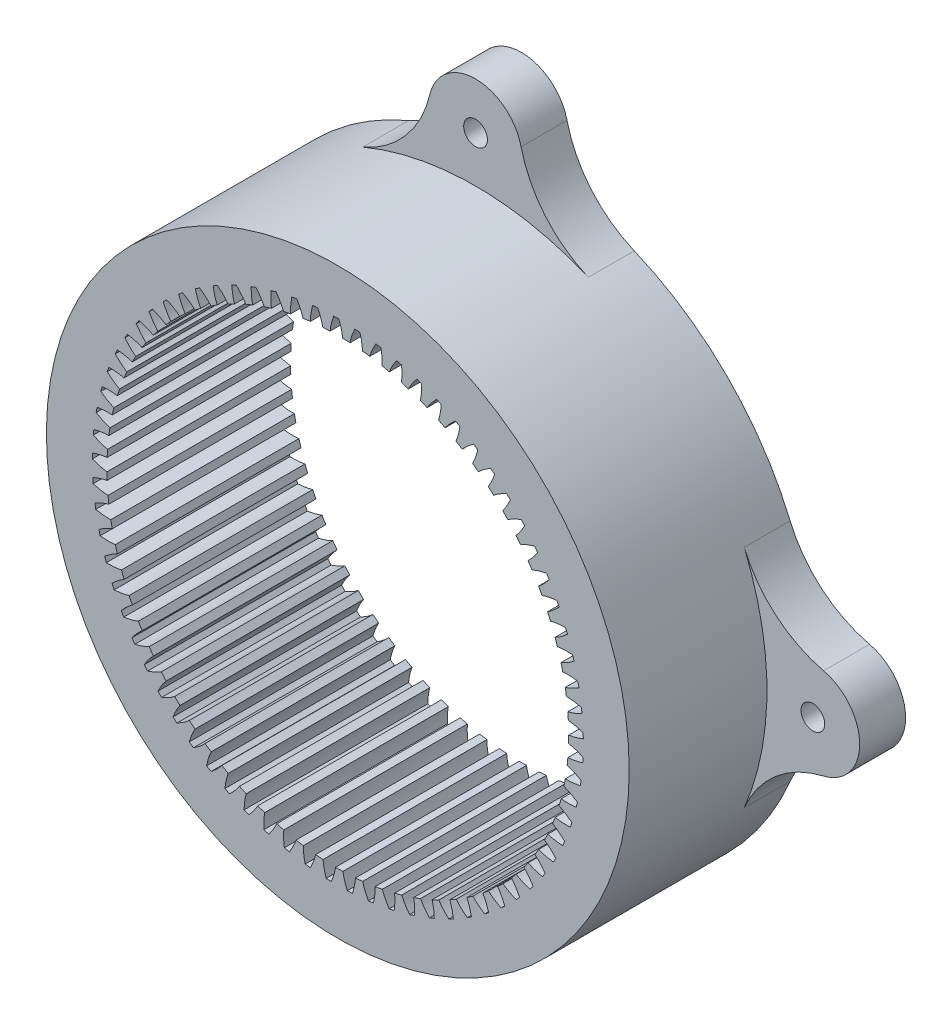
SolidWorks part; units mm, degrees
ref_plane "Front Plane" through (0, 0, 0) normal (0, 0, 1) x (1, 0, 0)
ref_plane "Top Plane" through (0, 0, 0) normal (0, 1, 0) x (1, 0, 0)
ref_plane "Right Plane" through (0, 0, 0) normal (1, 0, 0) x (0, 0, -1)
sketch "Sketch1" plane through (0, 0, 0) normal (0, 0, 1) x (1, 0, 0)
  circle A1 centre (0, 0) radius 38.0875
  dimension "D1" = 76.175
extrude "Boss-Extrude1" add sketch "Sketch1" along normal blind 24
sketch "Sketch2" plane through (0, 0, 24) normal (0, 0, 1) x (1, 0, 0)
  line L0 (0, 0) -> (38.0845, 0.4788) construction
  line L1 (0, 0) -> (38.0567, 1.5322) construction
  line L2 (0, 0) -> (37.9997, 2.5844) construction
  line L3 (4.4804, -8.2514) -> (4.4804, -8.1337) construction
  circle A0 centre (0, 0) radius 32.0875
  circle A1 centre (0, 0) radius 31.025 construction
  circle A2 centre (0, 0) radius 30.175
  circle A3 centre (0, 0) radius 29.9678 construction
  circle A4 centre (0, 0) radius 38.0875 construction
  spline S0 degree 4 poles (29.9678, 0) (29.99, 0.0005) (30.0521, 0.0032) (30.1692, 0.0142) (30.3596, 0.0402) (30.6006, 0.0851) (30.9099, 0.1568) (31.2707, 0.2585) (31.663, 0.3882) (32.0843, 0.5484) (32.4994, 0.7251) (32.9079, 0.9166) (33.3099, 1.1214) (33.7897, 1.3848) (34.3562, 1.724) (35.0016, 2.1498) (35.7167, 2.6727) (36.42, 3.2384) (37.098, 3.8335) (37.7517, 4.456) (38.3804, 5.1026) (38.91, 5.6892) (39.3478, 6.2034) (39.7045, 6.6428) (39.9809, 6.9942) (40.2576, 7.36) (40.5173, 7.7126) (40.7904, 8.0994) (41.0245, 8.4384) (41.3601, 8.9465) (41.5555, 9.2539) (41.8638, 9.751) (41.9939, 9.9761) (42.1149, 10.1791) (42.1485, 10.2393) (42.174, 10.2833) (42.1879, 10.307) knots 0 0 0 0 0 0.005377 0.015084 0.028532 0.04661 0.064855 0.092111 0.119476 0.146842 0.174209 0.201575 0.228941 0.256307 0.307035 0.361767 0.4165 0.471232 0.525964 0.580697 0.635429 0.690161 0.717528 0.744894 0.77226 0.799626 0.826992 0.854358 0.881725 0.909091 0.954545 0.977273 0.988636 0.994318 1 1 1 1 1 construction
  spline S1 degree 4 poles (29.9678, 0) (29.99, 0.0005) (30.0521, 0.0032) (30.1692, 0.0142) (30.3596, 0.0402) (30.6006, 0.0851) (30.9099, 0.1568) (31.2707, 0.2585) (31.663, 0.3882) (32.0843, 0.5484) (32.4994, 0.7251) (32.9079, 0.9166) (33.3099, 1.1214) (33.7897, 1.3848) (34.3562, 1.724) (35.0016, 2.1498) (35.7167, 2.6727) (36.42, 3.2384) (37.098, 3.8335) (37.7517, 4.456) (38.3804, 5.1026) (38.91, 5.6892) (39.3478, 6.2034) (39.7045, 6.6428) (39.9809, 6.9942) (40.2576, 7.36) (40.5173, 7.7126) (40.7904, 8.0994) (41.0245, 8.4384) (41.2405, 8.7654) (41.3534, 8.9391) (41.4088, 9.0254) knots 0 0 0 0 0 0.005377 0.015084 0.028532 0.04661 0.064855 0.092111 0.119476 0.146842 0.174209 0.201575 0.228941 0.256307 0.307035 0.361767 0.4165 0.471232 0.525964 0.580697 0.635429 0.690161 0.717528 0.744894 0.77226 0.799626 0.826992 0.854358 0.881725 0.909091 0.909091 0.909091 0.909091 0.909091
  spline S2 degree 4 poles (29.922, 1.6574) (29.9441, 1.6582) (30.0063, 1.6589) (30.1238, 1.6544) (30.3153, 1.639) (30.5585, 1.6074) (30.8712, 1.553) (31.2372, 1.4714) (31.636, 1.3635) (32.0655, 1.2269) (32.4898, 1.0734) (32.9082, 0.9049) (33.3209, 0.7226) (33.8146, 0.4861) (34.399, 0.1788) (35.0669, -0.2107) (35.8099, -0.6932) (36.5433, -1.2191) (37.2533, -1.7758) (37.9403, -2.3613) (38.6038, -2.9721) (39.165, -3.5285) (39.6307, -4.0177) (40.0111, -4.4367) (40.3065, -4.7723) (40.6031, -5.1222) (40.8818, -5.4599) (41.176, -5.831) (41.4284, -6.1566) (41.7916, -6.6453) (42.0037, -6.9414) (42.3391, -7.4207) (42.4813, -7.6383) (42.6134, -7.8343) (42.6503, -7.8926) (42.6782, -7.9351) (42.6934, -7.958) knots 0 0 0 0 0 0.005377 0.015084 0.028532 0.04661 0.064855 0.092111 0.119476 0.146842 0.174209 0.201575 0.228941 0.256307 0.307035 0.361767 0.4165 0.471232 0.525964 0.580697 0.635429 0.690161 0.717528 0.744894 0.77226 0.799626 0.826992 0.854358 0.881725 0.909091 0.954545 0.977273 0.988636 0.994318 1 1 1 1 1 construction
  spline S3 degree 4 poles (29.922, 1.6574) (29.9441, 1.6582) (30.0063, 1.6589) (30.1238, 1.6544) (30.3153, 1.639) (30.5585, 1.6074) (30.8712, 1.553) (31.2372, 1.4714) (31.636, 1.3635) (32.0655, 1.2269) (32.4898, 1.0734) (32.9082, 0.9049) (33.3209, 0.7226) (33.8146, 0.4861) (34.399, 0.1788) (35.0669, -0.2107) (35.8099, -0.6932) (36.5433, -1.2191) (37.2533, -1.7758) (37.9403, -2.3613) (38.6038, -2.9721) (39.165, -3.5285) (39.6307, -4.0177) (40.0111, -4.4367) (40.3065, -4.7723) (40.6031, -5.1222) (40.8818, -5.4599) (41.176, -5.831) (41.4284, -6.1566) (41.6622, -6.4711) (41.7845, -6.6383) (41.8446, -6.7214) knots 0 0 0 0 0 0.005377 0.015084 0.028532 0.04661 0.064855 0.092111 0.119476 0.146842 0.174209 0.201575 0.228941 0.256307 0.307035 0.361767 0.4165 0.471232 0.525964 0.580697 0.635429 0.690161 0.717528 0.744894 0.77226 0.799626 0.826992 0.854358 0.881725 0.909091 0.909091 0.909091 0.909091 0.909091
  point P6 (0, 0)
  dimension "D5" = 1.585
  dimension "D6" = 1.585
sketch "Sketch5" plane through (0, 0, 24) normal (0, 0, 1) x (1, 0, 0)
  circle A0 centre (0, 0) radius 30.175 construction
  circle A1 centre (0, 0) radius 30.175
extrude "Cut-Extrude1" cut sketch "Sketch5" against normal through all
sketch "Sketch6" plane through (0, 0, 24) normal (0, 0, 1) x (1, 0, 0)
  circle A0 centre (0, 0) radius 32.0875 construction
  arc A1 (32.0828, 0.5518) -> (32.0642, 1.2235) centre (0, 0) ccw
  spline S0 degree 4 poles (133.1254, -1995.4815) (26.6738, -33.7924) (26.6919, 0.8301) (28.5037, 1.7849) (30.3153, 1.639) (30.5585, 1.6074) (30.8712, 1.553) (31.2372, 1.4714) (31.636, 1.3635) (32.0655, 1.2269) (32.4898, 1.0734) (32.9082, 0.9049) (33.3209, 0.7226) (33.8146, 0.4861) (34.399, 0.1788) (35.0669, -0.2107) (35.8099, -0.6932) (36.5433, -1.2191) (37.2533, -1.7758) (37.9403, -2.3613) (38.6038, -2.9721) (39.165, -3.5285) (39.6307, -4.0177) (40.0111, -4.4367) (40.3065, -4.7723) (40.6031, -5.1222) (40.8818, -5.4599) (41.176, -5.831) (42.4699, -7.4998) (45.582, -12.0642) (7.971, 39.4031) (1213.0845, -1627.696) knots -0.394366 -0.394366 -0.394366 -0.394366 -0.394366 0.005377 0.015084 0.028532 0.04661 0.064855 0.092111 0.119476 0.146842 0.174209 0.201575 0.228941 0.256307 0.307035 0.361767 0.4165 0.471232 0.525964 0.580697 0.635429 0.690161 0.717528 0.744894 0.77226 0.799626 0.826992 0.854358 0.881725 1.360788 1.360788 1.360788 1.360788 1.360788 only from (29.922, 1.6574) to (41.8446, -6.7214) construction
  spline S1 degree 4 poles (22.5577, 1999.79) (24.764, 35.2159) (26.697, 0.6474) (28.5588, -0.2057) (30.3596, 0.0402) (30.6006, 0.0851) (30.9099, 0.1568) (31.2707, 0.2585) (31.663, 0.3882) (32.0843, 0.5484) (32.4994, 0.7251) (32.9079, 0.9166) (33.3099, 1.1214) (33.7897, 1.3848) (34.3562, 1.724) (35.0016, 2.1498) (35.7167, 2.6727) (36.42, 3.2384) (37.098, 3.8335) (37.7517, 4.456) (38.3804, 5.1026) (38.91, 5.6892) (39.3478, 6.2034) (39.7045, 6.6428) (39.9809, 6.9942) (40.2576, 7.36) (40.5173, 7.7126) (40.7904, 8.0994) (41.9901, 9.8372) (44.845, 14.5668) (10.1381, -38.902) (1121.205, 1692.2966) knots -0.394366 -0.394366 -0.394366 -0.394366 -0.394366 0.005377 0.015084 0.028532 0.04661 0.064855 0.092111 0.119476 0.146842 0.174209 0.201575 0.228941 0.256307 0.307035 0.361767 0.4165 0.471232 0.525964 0.580697 0.635429 0.690161 0.717528 0.744894 0.77226 0.799626 0.826992 0.854358 0.881725 1.360788 1.360788 1.360788 1.360788 1.360788 only from (29.9678, 0) to (41.4088, 9.0254) construction
  spline S2 degree 4 poles (29.922, 1.6574) (29.9441, 1.6582) (30.0063, 1.6589) (30.1238, 1.6544) (30.3153, 1.639) (30.5585, 1.6074) (30.8712, 1.553) (31.2372, 1.4714) (31.5815, 1.3783) (31.8503, 1.2949) (32.0108, 1.2416) (32.0642, 1.2235) knots 0 0 0 0 0 0.005377 0.015084 0.028532 0.04661 0.064855 0.092111 0.119476 0.13315 0.13315 0.13315 0.13315 0.13315
  spline S3 degree 4 poles (29.9678, 0) (29.99, 0.0005) (30.0521, 0.0032) (30.1692, 0.0142) (30.3596, 0.0402) (30.6006, 0.0851) (30.9099, 0.1568) (31.2707, 0.2585) (31.6094, 0.3705) (31.8732, 0.4686) (32.0305, 0.5307) (32.0828, 0.5518) knots 0 0 0 0 0 0.005377 0.015084 0.028532 0.04661 0.064855 0.092111 0.119476 0.13315 0.13315 0.13315 0.13315 0.13315
extrude "Cut-Extrude2" cut sketch "Sketch6" against normal through all and the other way through all
pattern_circular "CirPattern2" count 73 over 360 about axis through (0, 0, 24) along (0, 0, -1) of "Cut-Extrude2"
sketch "Sketch7" plane through (0, 0, 0) normal (0, 0, 1) x (1, 0, 0)
  line L0 (0, 0) -> (-44.0875, 0) construction
  line L1 (-44.0875, 6.1201) -> (-37.5926, 6.1201)
  line L2 (-44.0875, -6.1201) -> (-37.5926, -6.1201)
  circle A2 centre (-44.0875, 0) radius 1.55
  arc A3 (-44.0875, 6.1201) -> (-44.0875, -6.1201) centre (-44.0875, 0) ccw
  circle A5 centre (0, 0) radius 38.0875 construction
  arc A6 (-37.5926, 6.1201) -> (-37.5926, -6.1201) centre (0, 0) ccw
  dimension "D2" = 3.1
  dimension "D3" = 12.2403
  dimension "D1" = 44.0875
extrude "Boss-Extrude3" add sketch "Sketch7" along normal blind 6
fillet "Fillet1" radius 15 2 edges at (-37.5926, 6.1201, 3) (-37.5926, -6.1201, 3)
pattern_circular "CirPattern5" count 4 over 360 about axis through (0, 0, 0) along (0, 0, 1) of "Fillet1", "Boss-Extrude3"
ref_plane "Plane1" through (0, 0, 16) normal (0, 0, 1) x (1, 0, 0)
equation "\"P`\"= \"N\" / \"dp\"'Diametral pitch - number of teeth per mm"
equation "\"N\"= 73'# of teeth"
equation "\"phi\"= 15deg'Pressure angle"
equation "\"a\"= 1 / \"P`\"'Addendum"
equation "\"b\"= 1.25 / \"P`\"'Dedendum"
equation "\"c\"= \"b\" - \"a\"'clearance"
equation "\"dp\"= \"dp_from_mod\"'pitch cirle diameter"
equation "\"db\"= \"dp\" * cos ( \"phi\" )'base circle diameter"
equation "\"alpha\"= sqr ( \"dp\" ^ 2 - \"db\" ^ 2 ) / \"db\" * 180 / pi - \"phi\""
equation "\"D3@Sketch2\"= \"dp\"'Pitch circle dia"
equation "\"D4@Sketch2\"= \"dp\" - 2 * \"a\"'Tip circle (addendum) dia"
equation "\"D2@Sketch2\"= \"dp\" + 2 * \"b\"'Root circle (dedendum) dia"
equation "\"D1@Sketch2\"= \"db\""
equation "\"mod\"= 0.85mm'module - gear thickness"
equation "\"dp_from_mod\"= \"N\" * \"mod\""
equation "\"D5@Sketch2\" = 360 / ( 4 * \"N\" ) + \"alpha\""
equation "\"D6@Sketch2\"= 360 / ( 4 * \"N\" ) + \"alpha\""
equation "\"t_start\"= sqr ( ( \"AddendumDia\" / 2 ) ^ 2 - ( \"db\" / 2 ) ^ 2 ) / ( \"db\" / 2 )"
equation "\"AddendumDia\"= \"dp\" - 2 * \"a\""
equation "\"DedendumDia\"= \"dp\" + 2 * \"b\""
equation "\"D1@Sketch1\" = \"outermost_dia\""
equation "\"outermost_dia\"= \"DedendumDia\" + 12mm"
equation "\"D1@Sketch7\"= \"outermost_dia\" / 2 + 6mm"
